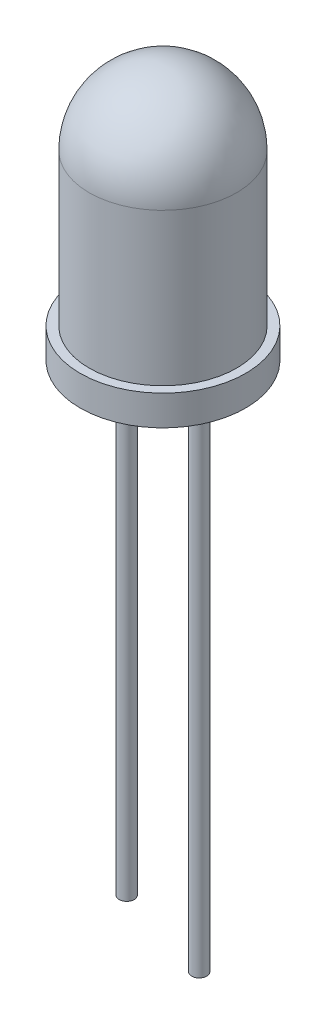
SolidWorks part; units mm, degrees
ref_plane "Alzado" through (0, 0, 0) normal (0, 0, 1) x (1, 0, 0)
ref_plane "Planta" through (0, 0, 0) normal (0, 1, 0) x (1, 0, 0)
ref_plane "Vista lateral" through (0, 0, 0) normal (1, 0, 0) x (0, 0, -1)
sketch "Croquis1" plane through (0, 0, 0) normal (0, 1, 0) x (1, 0, 0)
  circle A0 centre (0, 0) radius 2.75
  dimension "D1" = 5.5
extrude "Saliente-Extruir1" add sketch "Croquis1" along normal blind 1
sketch "Croquis2" plane through (0, 1, 0) normal (0, 1, 0) x (1, 0, 0)
  circle A0 centre (0, 0) radius 2.45
  dimension "D1" = 4.9
extrude "Saliente-Extruir2" add sketch "Croquis2" along normal blind 5.05 contours A0
dome "Cúpula1" faces to dome 1 distance 2.45 reverse direction no elliptical dome no face at (0, 6.05, 2.45) parameters "D1"=2.45
sketch "Croquis3" plane through (0, 0, 0) normal (0, -1, 0) x (1, 0, 0)
  line L0 (0, -3.025) -> (0, 3.025) construction
  circle A0 centre (-1.2052, 0) radius 0.25
  circle A1 centre (1.2052, 0) radius 0.25
  dimension "D1" = 0.5
extrude "Saliente-Extruir3" add sketch "Croquis3" along normal blind 16 contours A0
sketch "Croquis5" plane through (0, 0, 0) normal (0, -1, 0) x (1, 0, 0)
  circle A1 centre (1.2052, 0) radius 0.25
  circle A2 centre (1.2052, 0) radius 0.25
  dimension "D1" = 0
extrude "Saliente-Extruir5" add sketch "Croquis5" along normal blind 17
ref_plane "Plane1" through (0, 6.05, 0) normal (0, -1, 0) x (-1, 0, 0)
sketch "Sketch1" plane through (0, 6.05, 0) normal (0, -1, 0) x (-1, 0, 0)
  point P0 (0, 0)
